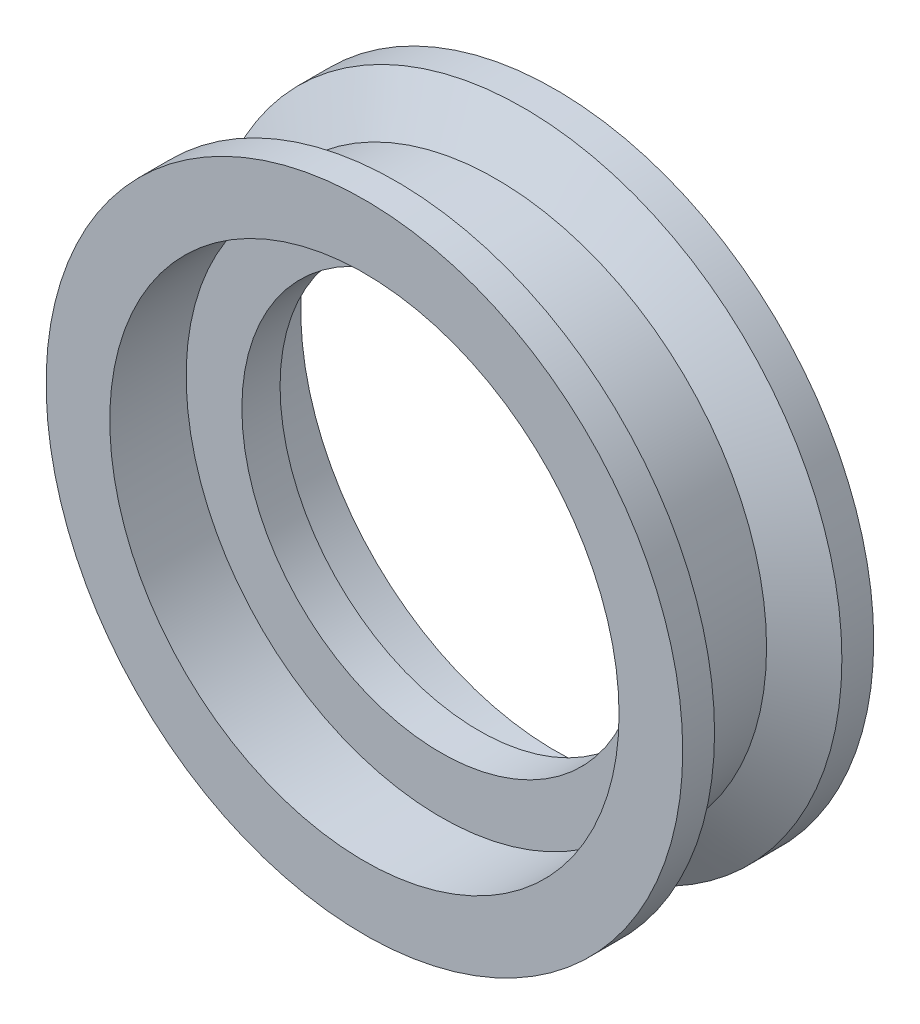
SolidWorks part; units mm, degrees
ref_plane "Front Plane" through (0, 0, 0) normal (0, 0, 1) x (1, 0, 0)
ref_plane "Top Plane" through (0, 0, 0) normal (0, 1, 0) x (1, 0, 0)
ref_plane "Right Plane" through (0, 0, 0) normal (1, 0, 0) x (0, 0, -1)
sketch "Sketch1" plane through (0, 0, 0) normal (0, 0, 1) x (1, 0, 0)
  line L0 (-1.5216, 1.9836) -> (-1.5216, -2.0164)
  line L1 (1.4783, 2.0161) -> (1.4783, -1.9839)
  circle A0 centre (0, 0) radius 10
  arc A2 (-1.5216, 1.9836) -> (1.4783, 2.0161) centre (0, 0) cw
  arc A3 (-1.5216, -2.0164) -> (1.4783, -1.9839) centre (-0.0433, -0.0002) ccw
extrude "Boss-Extrude1" add sketch "Sketch1" along normal mid plane 6
sketch "Sketch2" plane through (0, 0, 3) normal (0, 0, 1) x (1, 0, 0)
  circle A0 centre (0, 0) radius 8
  dimension "D1" = 16
extrude "Cut-Extrude1" cut sketch "Sketch2" against normal blind 2.4
sketch "Sketch3" plane through (0, 0, 0.6) normal (0, 0, 1) x (1, 0, 0)
  circle A0 centre (0, 6) radius 0.9
  dimension "D1" = 6
  dimension "D2" = 1.8
ref_plane "Plane1" through (-1.5216, -2.0164, 0.6) normal (0.8065, -0.5913, 0) x (0, 0, -1)
mirror "Mirror1" about plane through (0, 0, 0) normal (0, 0, 1) of "Cut-Extrude1"
sketch "Sketch5" plane through (0, 0, 0) normal (0, 1, 0) x (1, 0, 0)
  line L0 (0, 0) -> (0, 5.2467) construction
  line L1 (-10, 2) -> (-8.5, 1.134)
  line L2 (-10, 3) -> (-10, -3) construction
  line L3 (-8.5, 1.134) -> (-8.5, -1.134)
  line L4 (-8.5, -1.134) -> (-10, -2)
  line L5 (-10, -2) -> (-10, 2)
  point P10 (-10, 0)
  dimension "D1" = 1
  dimension "D2" = 1
  dimension "D3" = 60
  dimension "D4" = 60
  dimension "D5" = 1.5
revolve "Cut-Revolve1" cut sketch "Sketch5" angle 360 about L0
sketch "Sketch6" plane through (0, 0, -0.6) normal (0, 0, -1) x (-1, 0, 0)
  circle A0 centre (0, 0) radius 6.25
extrude "Cut-Extrude2" cut sketch "Sketch6" against normal through all
